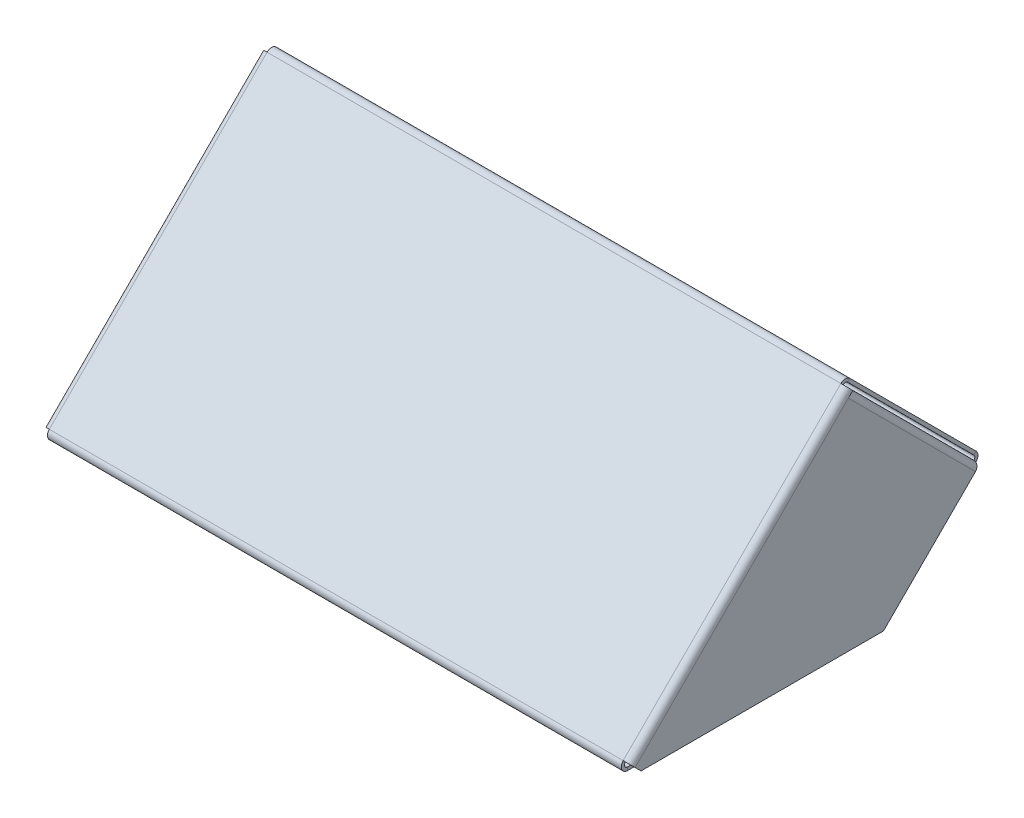
SolidWorks part; units mm, degrees
note: The reader was unsure of these and kept them because the rebuilt part matched: flange length of "Edge-Flange1", "Edge-Flange3", "Edge-Flange2", "Edge-Flange5", "Edge-Flange7", "Edge-Flange8", "Edge-Flange9", "Edge-Flange10".
ref_plane "Front Plane" through (0, 0, 0) normal (0, 0, 1) x (1, 0, 0)
ref_plane "Top Plane" through (0, 0, 0) normal (0, 1, 0) x (1, 0, 0)
ref_plane "Right Plane" through (0, 0, 0) normal (1, 0, 0) x (0, 0, -1)
sketch "Sketch1" plane through (0, 0, 0) normal (0, 1, 0) x (1, 0, 0)
  line L1 (-45, 20) -> (45, 20)
  line L2 (-45, 20) -> (-45, -20)
  line L3 (-45, -20) -> (45, -20)
  line L4 (45, 20) -> (45, -20)
  line L5 (-45, 20) -> (45, -20) construction
  line L6 (-45, -20) -> (45, 20) construction
  point P0 (0, 0)
base flange "Base-Flange1" sketch "Sketch1" thickness 0.5 reverse thickness direction no parameters "D1"=20
edge flange "Edge-Flange1" sketch "Sketch8" flange angle 45 flange length 50 flange position material outside bend radius 0.5 thickness 0.5 parameters "D6"=10
sketch "Sketch8" plane through (0, 0, 20) normal (0, -0.7071, -0.7071) x (-1, 0, 0)
  line L1 (45, 0) -> (-45, 0) construction
  line L2 (-45, 0) -> (-45, 50)
  line L3 (-45, 50) -> (45, 50)
  line L4 (45, 50) -> (45, 0)
  line L5 (45, 0) -> (-45, 0)
bend "EdgeBend1" bend radius 0.5 bend angle 135 parameters "D5"=1
edge flange "Edge-Flange3" sketch "Sketch22" flange angle 135 flange length 10 flange position material outside bend radius 0.5 thickness 0.5 parameters "D6"=10
sketch "Sketch22" plane through (0, 0, -20) normal (0, -0.7071, -0.7071) x (-1, 0, 0)
  line L0 (-45, 0) -> (45, 0) construction
  line L1 (-45, 0) -> (45, 0)
  line L2 (-45, 0) -> (-45, 10)
  line L3 (-45, 10) -> (45, 10)
  line L4 (45, 10) -> (45, 0)
bend "EdgeBend3" bend radius 0.5 bend angle 45 parameters "D5"=3
edge flange "Edge-Flange2" sketch "Sketch17" flange angle 90 flange length 29 flange position material outside bend radius 0.5 thickness 0.5 parameters "D6"=10
sketch "Sketch17" plane through (0, 35.3553, -15.3553) normal (0, -0.7071, 0.7071) x (-1, 0, 0)
  line L1 (45, 0) -> (-45, 0) construction
  line L2 (-45, 0) -> (-45, 29)
  line L3 (-45, 29) -> (45, 29)
  line L4 (45, 29) -> (45, 0)
  line L5 (45, 0) -> (-45, 0)
bend "EdgeBend2" bend radius 0.5 bend angle 90 parameters "D5"=2
edge flange "Edge-Flange5" sketch "Sketch32" flange angle 90 flange length 21 flange position material outside bend radius 0.5 thickness 0.5 parameters "D6"=10
sketch "Sketch32" plane through (0, 14.8492, -35.8614) normal (0, 0.7071, 0.7071) x (-1, 0, 0)
  line L1 (45, 0) -> (-45, 0) construction
  line L2 (-45, 0) -> (-45, 21)
  line L3 (-45, 21) -> (45, 21)
  line L4 (45, 21) -> (45, 0)
  line L5 (45, 0) -> (-45, 0)
bend "EdgeBend5" bend radius 0.5 bend angle 90 parameters "D5"=4
edge flange "Edge-Flange7" sketch "Sketch44" flange angle 90 flange length 28.8 flange position bend outside bend radius 0.5 thickness 0.5 parameters "D6"=10
sketch "Sketch44" plane through (-45, 10, 10) normal (1, 0, 0) x (0, -0.7071, 0.7071)
  line L1 (12.935, 0) -> (-35.3579, 0) construction
  line L2 (-35.3579, 0) -> (-35.3579, 28.8)
  line L3 (-35.3579, 28.8) -> (12.935, 28.8)
  line L4 (12.935, 28.8) -> (12.935, 0)
  line L5 (12.935, 0) -> (-35.3579, 0)
bend "EdgeBend7" bend radius 0.5 bend angle 90 parameters "D5"=5
edge flange "Edge-Flange8" sketch "Sketch49" flange angle 90 flange length 28.8 flange position bend outside bend radius 0.6 thickness 0.5 parameters "D6"=10
sketch "Sketch49" plane through (45, 10, 10) normal (-1, 0, 0) x (0, 0.7071, -0.7071)
  line L1 (35.3579, 0) -> (-12.935, 0) construction
  line L2 (-12.935, 0) -> (-12.935, 28.8)
  line L3 (-12.935, 28.8) -> (35.3579, 28.8)
  line L4 (35.3579, 28.8) -> (35.3579, 0)
  line L5 (35.3579, 0) -> (-12.935, 0)
bend "EdgeBend8" bend radius 0.6 bend angle 90 parameters "D5"=6
sketch "Sketch52" plane through (-46, 0, 0) normal (-1, 0, 0) x (0, 0, 1)
  line L0 (-20.2294, -0.5) -> (17.7929, -0.5)
  line L1 (-19.7929, -0.5) -> (18.7929, -0.5) construction
  line L2 (18.7929, 0.5) -> (-1.2182, -19.5111) construction
  line L3 (-20.2294, -0.5) -> (-1.2182, -19.5111)
  line L4 (-1.2182, -19.5111) -> (17.7929, -0.5)
extrude "Cut-Extrude3" cut sketch "Sketch52" against normal through all normal cut yes
edge flange "Edge-Flange9" sketch "Sketch57" flange angle 90 flange length 10 flange position material inside bend radius 0.5 thickness 0.5 relief none parameters "D6"=10
sketch "Sketch57" plane through (-45.5, 25.0018, -25.0018) normal (0, 0.7071, -0.7071) x (0, 0.7071, 0.7071)
  line L2 (-14.6579, 0) -> (-14.6579, 10)
  line L3 (-14.6579, 10) -> (13.6421, 10)
  line L4 (13.6421, 10) -> (13.6421, 0)
  line L5 (-14.6579, 0) -> (13.6421, 0) construction
  line L6 (-14.6579, 0) -> (13.6421, 0)
bend "EdgeBend9" bend radius 0.5 bend angle 90 parameters "D5"=7
edge flange "Edge-Flange10" sketch "Sketch62" flange angle 90 flange length 10 flange position material inside bend radius 0.5 thickness 0.5 relief none parameters "D6"=10
sketch "Sketch62" plane through (45.6, 25.0018, -25.0018) normal (0, 0.7071, -0.7071) x (0, -0.7071, -0.7071)
  line L2 (-13.5421, 0) -> (-13.5421, 10)
  line L3 (-13.5421, 10) -> (14.6579, 10)
  line L4 (14.6579, 10) -> (14.6579, 0)
  line L5 (-13.5421, 0) -> (14.6579, 0) construction
  line L6 (-13.5421, 0) -> (14.6579, 0)
bend "EdgeBend10" bend radius 0.5 bend angle 90 parameters "D5"=8
sketch "Sketch65" plane through (0, -0.5, 0) normal (0, -1, 0) x (1, 0, 0)
  line L0 (-45, 2.0723) -> (45, 2.0723) construction
  line L3 (-41, 2.0723) -> (-41, 27.0199) construction
  line L4 (-45, -19.7929) -> (-45, 18.7929) construction
  line L5 (0, 0) -> (0, 36.4335) construction
  line L6 (41, 2.0723) -> (41, 27.0199) construction
  circle A0 centre (-41, 9.5919) radius 1.5
  circle A1 centre (41, 9.5919) radius 1.5
  circle A2 centre (-41, -12.9277) radius 1.5
  circle A3 centre (41, -12.9277) radius 1.5
  dimension "D2" = 15
  dimension "D1" = 4
extrude "Cut-Extrude4" cut sketch "Sketch65" against normal blind 5 normal cut yes
sketch "Bend-Lines1" [suppressed] plane through (0, 0, 0) normal (0, 1, 0) x (1, 0, 0)
sketch "Bounding-Box1" [suppressed] plane through (0, 0, 0) normal (0, 1, 0) x (1, 0, 0)
sheet metal parameters "Sheet-Metal(1)" thickness 0.5 parameters "D1"=20
flat pattern "Flat-Pattern(1)" [suppressed]
sketch "Bend-Lines2" plane through (0, 0, 0) normal (0, 1, 0) x (1, 0, 0)
sketch "Bounding-Box2" [suppressed] plane through (0, 0, 0) normal (0, 1, 0) x (1, 0, 0)
sheet metal parameters "Sheet-Metal(2)" thickness 0.5 parameters "D1"=20
flat pattern "Flat-Pattern(1)" [suppressed]
sketch "Bend-Lines3" plane through (0, 0, 0) normal (0, 1, 0) x (1, 0, 0)
sketch "Bounding-Box3" [suppressed] plane through (0, 0, 0) normal (0, 1, 0) x (1, 0, 0)
bend of the flat pattern "Flatten-<EdgeBend1>1"
sheet metal parameters "Sheet-Metal(3)" thickness 0.5 parameters "D1"=20
flat pattern "Flat-Pattern(1)" [suppressed]
sketch "Bend-Lines4" plane through (0, 0, 0) normal (0, 1, 0) x (1, 0, 0)
sketch "Bounding-Box4" [suppressed] plane through (0, 0, 0) normal (0, 1, 0) x (1, 0, 0)
bend of the flat pattern "Flatten-<EdgeBend1>2"
bend of the flat pattern "Flatten-<EdgeBend2>1"
bend of the flat pattern "Flatten-<EdgeBend3>2"
sheet metal parameters "Sheet-Metal(4)" thickness 0.5 parameters "D1"=20
flat pattern "Flat-Pattern(1)" [suppressed]
sketch "Bend-Lines5" plane through (0, 0, 0) normal (0, 1, 0) x (1, 0, 0)
sketch "Bounding-Box5" [suppressed] plane through (0, 0, 0) normal (0, 1, 0) x (1, 0, 0)
bend of the flat pattern "Flatten-<EdgeBend1>3"
bend of the flat pattern "Flatten-<EdgeBend3>1"
sheet metal parameters "Sheet-Metal(6)" thickness 0.5 parameters "D1"=20
flat pattern "Flat-Pattern(1)" [suppressed]
sketch "Bend-Lines7" plane through (0, 0, 0) normal (0, 1, 0) x (1, 0, 0)
sketch "Bounding-Box7" [suppressed] plane through (0, 0, 0) normal (0, 1, 0) x (1, 0, 0)
bend of the flat pattern "Flatten-<EdgeBend1>5"
bend of the flat pattern "Flatten-<EdgeBend2>4"
bend of the flat pattern "Flatten-<EdgeBend3>4"
bend of the flat pattern "Flatten-<EdgeBend5>1"
sheet metal parameters "Sheet-Metal(8)" thickness 0.5 parameters "D1"=20
flat pattern "Flat-Pattern(1)" [suppressed]
sketch "Bend-Lines9" plane through (0, 0, 0) normal (0, 1, 0) x (1, 0, 0)
sketch "Bounding-Box9" [suppressed] plane through (0, 0, 0) normal (0, 1, 0) x (1, 0, 0)
bend of the flat pattern "Flatten-<EdgeBend1>7"
bend of the flat pattern "Flatten-<EdgeBend2>6"
bend of the flat pattern "Flatten-<EdgeBend3>6"
bend of the flat pattern "Flatten-<EdgeBend5>3"
bend of the flat pattern "Flatten-<EdgeBend7>1"
sheet metal parameters "Sheet-Metal(9)" thickness 0.5 parameters "D1"=20
flat pattern "Flat-Pattern(1)" [suppressed]
sketch "Bend-Lines10" plane through (0, 0, 0) normal (0, 1, 0) x (1, 0, 0)
sketch "Bounding-Box10" [suppressed] plane through (0, 0, 0) normal (0, 1, 0) x (1, 0, 0)
bend of the flat pattern "Flatten-<EdgeBend1>8"
bend of the flat pattern "Flatten-<EdgeBend2>7"
bend of the flat pattern "Flatten-<EdgeBend3>7"
bend of the flat pattern "Flatten-<EdgeBend5>4"
bend of the flat pattern "Flatten-<EdgeBend7>2"
bend of the flat pattern "Flatten-<EdgeBend8>1"
sheet metal parameters "Sheet-Metal(10)" thickness 0.5 parameters "D1"=20
flat pattern "Flat-Pattern(1)"
sketch "Bend-Lines11" plane through (0, 0, 0) normal (0, 1, 0) x (1, 0, 0)
  line L0 (45.6676, -68.8529) -> (45.6676, -20.56) construction
  line L1 (-45.589, -20.56) -> (-45.589, -68.8529) construction
  line L2 (-45, -98.6201) -> (45, -98.6201) construction
  line L3 (45, 20.0874) -> (-45, 20.0874) construction
  line L4 (-45, -69.442) -> (45, -69.442) construction
  line L5 (-45, -19.6765) -> (45, -19.6765) construction
  line L6 (45.6676, -68.8529) -> (45.6676, -20.56) construction
  line L7 (-45.589, -20.56) -> (-45.589, -68.8529) construction
  line L8 (-45, -98.6201) -> (45, -98.6201) construction
  line L9 (45, 20.0874) -> (-45, 20.0874) construction
  line L10 (-45, -69.442) -> (45, -69.442) construction
  line L11 (-45, -19.6765) -> (45, -19.6765) construction
sketch3d "Bounding-Box11" [suppressed]
  line L0 (-74.4781, 30.1748, 0) -> (-74.4781, -119.7091, 0) construction
  line L1 (74.5352, 30.1748, 0) -> (74.5352, -119.7091, 0) construction
  line L2 (-74.4781, 30.1748, 0) -> (74.5352, 30.1748, 0) construction
  line L3 (-74.4781, -119.7091, 0) -> (74.5352, -119.7091, 0) construction
bend of the flat pattern "Flatten-<EdgeBend1>9"
bend of the flat pattern "Flatten-<EdgeBend2>8"
bend of the flat pattern "Flatten-<EdgeBend3>8"
bend of the flat pattern "Flatten-<EdgeBend5>5"
bend of the flat pattern "Flatten-<EdgeBend7>3"
bend of the flat pattern "Flatten-<EdgeBend8>2"
sheet metal parameters "Sheet-Metal(11)" thickness 0.5 parameters "D1"=20
flat pattern "Flat-Pattern(1)" [suppressed]
sketch "Bend-Lines12" plane through (0, 0, 0) normal (0, 1, 0) x (1, 0, 0)
sketch "Bounding-Box12" [suppressed] plane through (0, 0, 0) normal (0, 1, 0) x (1, 0, 0)
bend of the flat pattern "Flatten-<EdgeBend8>3"
bend of the flat pattern "Flatten-<EdgeBend7>4"
bend of the flat pattern "Flatten-<EdgeBend5>6"
bend of the flat pattern "Flatten-<EdgeBend3>9"
bend of the flat pattern "Flatten-<EdgeBend2>9"
bend of the flat pattern "Flatten-<EdgeBend1>10"
bend of the flat pattern "Flatten-<EdgeBend9>1"
sheet metal parameters "Sheet-Metal(12)" thickness 0.5 parameters "D1"=20
flat pattern "Flat-Pattern(1)"
sketch "Bend-Lines13" plane through (0, 0, 0) normal (0, 1, 0) x (1, 0, 0)
  line L0 (46.3352, -68.442) -> (74.5352, -68.442) construction
  line L1 (-74.4781, -68.442) -> (-46.1781, -68.442) construction
  line L2 (45.6676, -68.8529) -> (45.6676, -20.56) construction
  line L3 (-45.589, -68.8529) -> (-45.589, -20.56) construction
  line L4 (-45, -98.6201) -> (45, -98.6201) construction
  line L5 (45, 20.0874) -> (-45, 20.0874) construction
  line L6 (-45, -69.442) -> (45, -69.442) construction
  line L7 (-45, -19.6765) -> (45, -19.6765) construction
  line L8 (46.3352, -68.442) -> (74.5352, -68.442) construction
  line L9 (-74.4781, -68.442) -> (-46.1781, -68.442) construction
  line L10 (45.6676, -68.8529) -> (45.6676, -20.56) construction
  line L11 (-45.589, -68.8529) -> (-45.589, -20.56) construction
  line L12 (-45, -98.6201) -> (45, -98.6201) construction
  line L13 (45, 20.0874) -> (-45, 20.0874) construction
  line L14 (-45, -69.442) -> (45, -69.442) construction
  line L15 (-45, -19.6765) -> (45, -19.6765) construction
sketch3d "Bounding-Box13" [suppressed]
  line L0 (-74.4781, 30.1748, 0) -> (-74.4781, -119.7091, 0) construction
  line L1 (74.5352, 30.1748, 0) -> (74.5352, -119.7091, 0) construction
  line L2 (-74.4781, 30.1748, 0) -> (74.5352, 30.1748, 0) construction
  line L3 (-74.4781, -119.7091, 0) -> (74.5352, -119.7091, 0) construction
bend of the flat pattern "Flatten-<EdgeBend8>4"
bend of the flat pattern "Flatten-<EdgeBend7>5"
bend of the flat pattern "Flatten-<EdgeBend5>7"
bend of the flat pattern "Flatten-<EdgeBend3>10"
bend of the flat pattern "Flatten-<EdgeBend2>10"
bend of the flat pattern "Flatten-<EdgeBend1>11"
bend of the flat pattern "Flatten-<EdgeBend9>2"
bend of the flat pattern "Flatten-<EdgeBend10>1"
sheet metal parameters "Sheet-Metal(13)" thickness 0.5 parameters "D1"=20
flat pattern "Flat-Pattern(1)" [suppressed]
sketch "Bend-Lines14" plane through (0, 0, 0) normal (0, 1, 0) x (1, 0, 0)
sketch "Bounding-Box14" [suppressed] plane through (0, 0, 0) normal (0, 1, 0) x (1, 0, 0)
bend of the flat pattern "Flatten-<EdgeBend10>2"
bend of the flat pattern "Flatten-<EdgeBend9>3"
bend of the flat pattern "Flatten-<EdgeBend8>5"
bend of the flat pattern "Flatten-<EdgeBend7>6"
bend of the flat pattern "Flatten-<EdgeBend5>8"
bend of the flat pattern "Flatten-<EdgeBend3>11"
bend of the flat pattern "Flatten-<EdgeBend2>11"
bend of the flat pattern "Flatten-<EdgeBend1>12"
